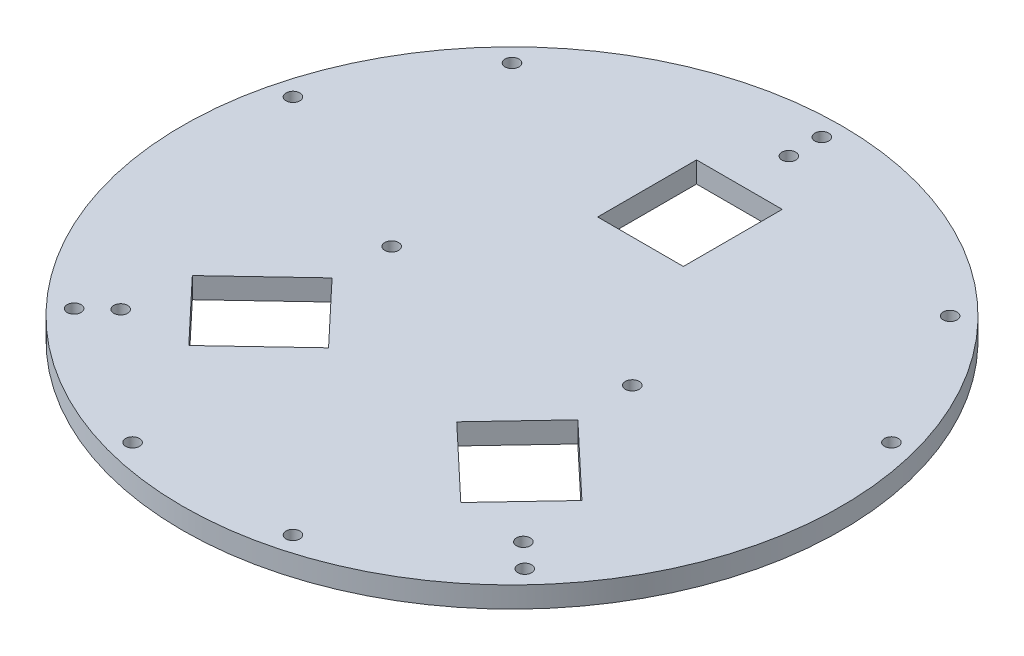
SolidWorks part; units mm, degrees
ref_plane "Front Plane" through (0, 0, 0) normal (0, 0, 1) x (1, 0, 0)
ref_plane "Top Plane" through (0, 0, 0) normal (0, 1, 0) x (1, 0, 0)
ref_plane "Right Plane" through (0, 0, 0) normal (1, 0, 0) x (0, 0, -1)
sketch "Sketch1" plane through (0, 0, 0) normal (0, 1, 0) x (1, 0, 0)
  line L0 (0, 100) -> (0, -100) construction
  line L11 (0, 0) -> (91.8216, 39.608) construction
  line L12 (0, 0) -> (-91.8216, 39.608) construction
  line L13 (19.4464, -36.2193) -> (59.1099, -37.8948) construction
  line L14 (-13, 69) -> (13, 69)
  line L15 (-13, 69) -> (-13, 39)
  line L16 (-13, 39) -> (13, 39)
  line L17 (13, 69) -> (13, 39)
  line L18 (-13, 69) -> (13, 39) construction
  line L19 (-13, 39) -> (13, 69) construction
  line L20 (41.2676, -56.8065) -> (37.2887, -17.3076) construction
  line L21 (59.1099, -37.8948) -> (37.2887, -17.3076)
  line L22 (19.4464, -36.2193) -> (37.2887, -17.3076)
  line L23 (41.2676, -56.8065) -> (19.4464, -36.2193)
  line L24 (41.2676, -56.8065) -> (59.1099, -37.8948)
  line L25 (-37.2887, -17.3076) -> (-41.2676, -56.8065) construction
  line L26 (-59.1099, -37.8948) -> (-19.4464, -36.2193) construction
  line L27 (-41.2676, -56.8065) -> (-19.4464, -36.2193)
  line L28 (-37.2887, -17.3076) -> (-19.4464, -36.2193)
  line L29 (-59.1099, -37.8948) -> (-37.2887, -17.3076)
  line L30 (-59.1099, -37.8948) -> (-41.2676, -56.8065)
  circle A0 centre (0, 0) radius 100
  circle A5 centre (0, 94) radius 2.1
  circle A6 centre (0, 84) radius 2.1
  circle A7 centre (61.0994, -57.6443) radius 2.1
  circle A8 centre (68.3731, -64.5067) radius 2.1
  circle A9 centre (-68.3731, -64.5067) radius 2.1
  circle A10 centre (-61.0994, -57.6443) radius 2.1
  point P29 (0, 54)
  point P38 (39.2782, -37.057)
  point P43 (-39.2782, -37.057)
  point P46 (0, 0)
  dimension "D1" = 200
  dimension "D6" = 4.2
  dimension "D2" = 66.667
  dimension "D7" = 6
  dimension "D8" = 10
  dimension "D10" = 30
  dimension "D11" = 26
  dimension "D12" = 15
extrude "Boss-Extrude1" add sketch "Sketch1" along normal blind 6.35
sketch "Sketch2" plane through (0, 6.35, 0) normal (0, 1, 0) x (1, 0, 0)
  line L0 (0, 0) -> (0, -100) construction
  line L1 (0, 0) -> (-25.8819, -96.5926) construction
  circle A0 centre (0, 0) radius 100 construction
  circle A1 centre (-24.329, -90.797) radius 2.1
  circle A2 centre (24.329, -90.797) radius 2.1
  circle A3 centre (-66.468, 66.468) radius 2.1
  circle A4 centre (-90.797, 24.329) radius 2.1
  circle A5 centre (90.797, 24.329) radius 2.1
  circle A6 centre (66.468, 66.468) radius 2.1
  point P22 (0, 0)
  dimension "D4" = 4.2
  dimension "D1" = 15
  dimension "D5" = 6
  dimension "D6" = 3
extrude "Cut-Extrude1" cut sketch "Sketch2" against normal up to surface (6.35 mm away) up to face at (39.2782, 0, 37.057)
sketch "Sketch3" plane through (0, 6.35, 0) normal (0, 1, 0) x (1, 0, 0)
  line L0 (-100, 0) -> (100, 0) construction
  line L1 (0, -100) -> (0, 100) construction
  circle A0 centre (0, 0) radius 100 construction
  circle A1 centre (36.5, 0) radius 2.1
  circle A2 centre (-36.5, 0) radius 2.1
  dimension "D2" = 4.2
  dimension "D1" = 36.5
extrude "Cut-Extrude2" cut sketch "Sketch3" against normal up to surface (6.35 mm away) up to face at (90.797, 0, -22.229)
